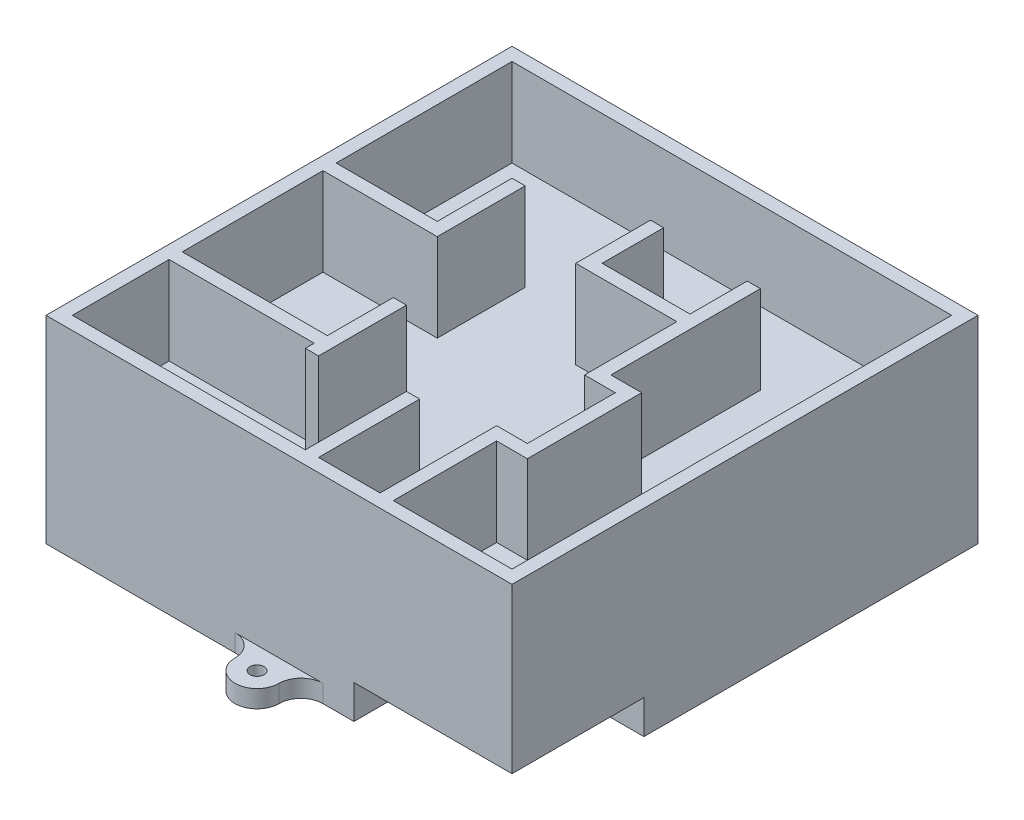
SolidWorks part; units mm, degrees
ref_plane "Front Plane" through (0, 0, 0) normal (0, 0, 1) x (1, 0, 0)
ref_plane "Top Plane" through (0, 0, 0) normal (0, 1, 0) x (1, 0, 0)
ref_plane "Right Plane" through (0, 0, 0) normal (1, 0, 0) x (0, 0, -1)
sketch "Sketch2" plane through (0, 0, 0) normal (0, 1, 0) x (1, 0, 0)
  line L1 (0, 0) -> (106, 0)
  line L2 (0, 0) -> (0, 106)
  line L3 (0, 106) -> (106, 106)
  line L4 (106, 0) -> (106, 106)
  circle A0 centre (18, 15) radius 4
  circle A1 centre (92, 13.5) radius 6
  dimension "D3" = 8
  dimension "D4" = 12
  dimension "D5" = 15
  dimension "D6" = 18
  dimension "D7" = 13.5
  dimension "D8" = 14
  dimension "D1" = 106
  dimension "D2" = 106
extrude "Boss-Extrude1" add sketch "Sketch2" along normal blind 25
sketch "Sketch3" plane through (0, 25, 0) normal (0, 1, 0) x (1, 0, 0)
  line L0 (3, 103) -> (3, 3)
  line L1 (0, 106) -> (106, 106)
  line L2 (0, 106) -> (0, 0)
  line L3 (0, 0) -> (106, 0)
  line L4 (106, 106) -> (106, 0)
  line L5 (3, 3) -> (103, 3)
  line L6 (103, 103) -> (103, 3)
  line L7 (3, 103) -> (103, 103)
  dimension "D1" = 3
extrude "Boss-Extrude2" add sketch "Sketch3" along normal blind 20
sketch "Sketch5" plane through (0, 25, 0) normal (0, 1, 0) x (1, 0, 0)
  line L2 (3, 28) -> (3, 25)
  line L5 (3, 103) -> (3, 3) construction
  line L6 (83, 52.5) -> (83, 26.5)
  line L9 (36, 43) -> (39, 43)
  line L10 (39, 23) -> (39, 43)
  line L12 (3, 63) -> (3, 60)
  line L19 (26, 63) -> (26, 80)
  line L20 (3, 3) -> (103, 3) construction
  line L21 (56, 3) -> (59, 3)
  line L22 (56, 3) -> (56, 26)
  line L23 (56, 26) -> (59, 26)
  line L24 (59, 3) -> (59, 26)
  line L25 (3, 28) -> (36, 28)
  line L26 (3, 3) -> (103, 3) construction
  line L27 (73, 3) -> (76, 3)
  line L30 (76, 3) -> (76, 26.5)
  line L38 (80, 29.5) -> (80, 49.5)
  line L41 (80, 49.5) -> (73, 49.5)
  line L42 (73, 52.5) -> (73, 49.5)
  line L44 (76, 26.5) -> (83, 26.5)
  line L45 (73, 52.5) -> (83, 52.5)
  line L47 (3, 63) -> (26, 63)
  line L50 (80, 29.5) -> (73, 29.5)
  line L51 (73, 29.5) -> (73, 3)
  line L52 (29, 60) -> (3, 60)
  line L53 (29, 60) -> (29, 80)
  line L54 (29, 80) -> (26, 80)
  line L55 (36, 43) -> (36, 28)
  line L56 (3, 25) -> (36, 25)
  line L57 (36, 25) -> (36, 23)
  line L58 (36, 23) -> (39, 23)
  dimension "D3" = 0
extrude "Boss-Extrude3" add sketch "Sketch5" along normal blind 20 contours L9 L10 L58 L57 L56 L2 L25 L55 | L54 L19 L47 L12 L52 L53 | L22 L21 L24 L23 | L51 L27 L30 L44 L6 L45 L42 L41 L38 L50
sketch "Sketch7" plane through (0, 25, 0) normal (0, 1, 0) x (1, 0, 0)
  line L1 (73, 52.5) -> (76, 52.5)
  line L2 (73, 52.5) -> (73, 86.5)
  line L3 (73, 86.5) -> (76, 86.5)
  line L4 (76, 52.5) -> (76, 86.5)
  line L5 (73, 73.4965) -> (53, 73.4965)
  line L6 (73, 73.4965) -> (73, 70.4965)
  line L7 (73, 70.4965) -> (53, 70.4965)
  line L8 (53, 73.4965) -> (53, 70.4965)
  line L9 (53, 70.4965) -> (50, 70.4965)
  line L10 (53, 70.4965) -> (53, 87.4965)
  line L11 (53, 87.4965) -> (50, 87.4965)
  line L12 (50, 70.4965) -> (50, 87.4965)
  line M14 (73, 52.5) -> (83, 52.5)
  dimension "D1" = 3
  dimension "D2" = 3
  dimension "D3" = 3
  dimension "D4" = 34
  dimension "D5" = 20
  dimension "D6" = 17
extrude "Boss-Extrude4" add sketch "Sketch7" along normal blind 20 contours L12 L9 L8 L10 L11 | L5 L8 L7 L2 | L4 L3 L2 M14 region at (74.5, 25, -69.5) region at (63, 25, -71.9965) region at (51.5, 25, -78.9965)
sketch "Sketch10" plane through (0, 0, 0) normal (0, 0, 1) x (1, 0, 0)
  line L0 (0, 0) -> (106, 0) construction
  line L1 (48, 4) -> (58, 4)
  line L2 (48, 4) -> (48, 0)
  line L3 (48, 0) -> (58, 0)
  line L4 (58, 4) -> (58, 0)
  line L5 (0, 45) -> (106, 45) construction
  point P6 (53, 4)
  point P9 (53, 45)
  dimension "D1" = 10
  dimension "D2" = 4
  dimension "D3" = 0
  dimension "D4" = 0
extrude "Boss-Extrude5" add sketch "Sketch10" along normal blind 10
sketch "Sketch11" plane through (0, 0, -106) normal (0, 0, -1) x (-1, 0, 0)
  line L0 (-106, 45) -> (0, 45) construction
  line L1 (-58, 4) -> (-48, 4)
  line L2 (-58, 4) -> (-58, 0)
  line L3 (-58, 0) -> (-48, 0)
  line L4 (-48, 4) -> (-48, 0)
  line L5 (-106, 0) -> (0, 0) construction
  point P4 (-53, 4)
  point P7 (-53, 45)
  dimension "D1" = 10
  dimension "D2" = 4
  dimension "D3" = 0
  dimension "D4" = 0
extrude "Boss-Extrude6" add sketch "Sketch11" along normal blind 10
fillet "Fillet2" 2 edges at (48, 2, -116) (58, 2, -116) type full round first side face at (48, 2, -111) second side face at (58, 2, -111) middle face at (53, 2, -116)
fillet "Fillet3" radius 5 2 edges at (48, 2, -106) (58, 2, -106)
fillet "Fillet4" radius 5 2 edges at (48, 2, 0) (58, 2, 0)
fillet "Fillet5" 2 edges at (48, 2, 10) (58, 2, 10) type full round first side face at (48, 2, 7.5) second side face at (58, 2, 7.5) middle face at (53, 2, 10)
sketch "Sketch13" plane through (0, 4, 0) normal (0, 1, 0) x (1, 0, 0)
  circle A0 centre (53, -5) radius 1.6
  circle A1 centre (53, 111) radius 1.6
  dimension "D1" = 3.2
  dimension "D2" = 3.2
extrude "Cut-Extrude2" cut sketch "Sketch13" against normal through all
sketch "Sketch14" plane through (0, 0, 0) normal (0, 0, 1) x (1, 0, 0)
  line L1 (106, 0) -> (70.0395, 0)
  line L2 (106, 0) -> (106, 7.6935)
  line L3 (106, 7.6935) -> (70.0395, 7.6935)
  line L4 (70.0395, 0) -> (70.0395, 7.6935)
extrude "Cut-Extrude3" cut sketch "Sketch14" against normal blind 30
